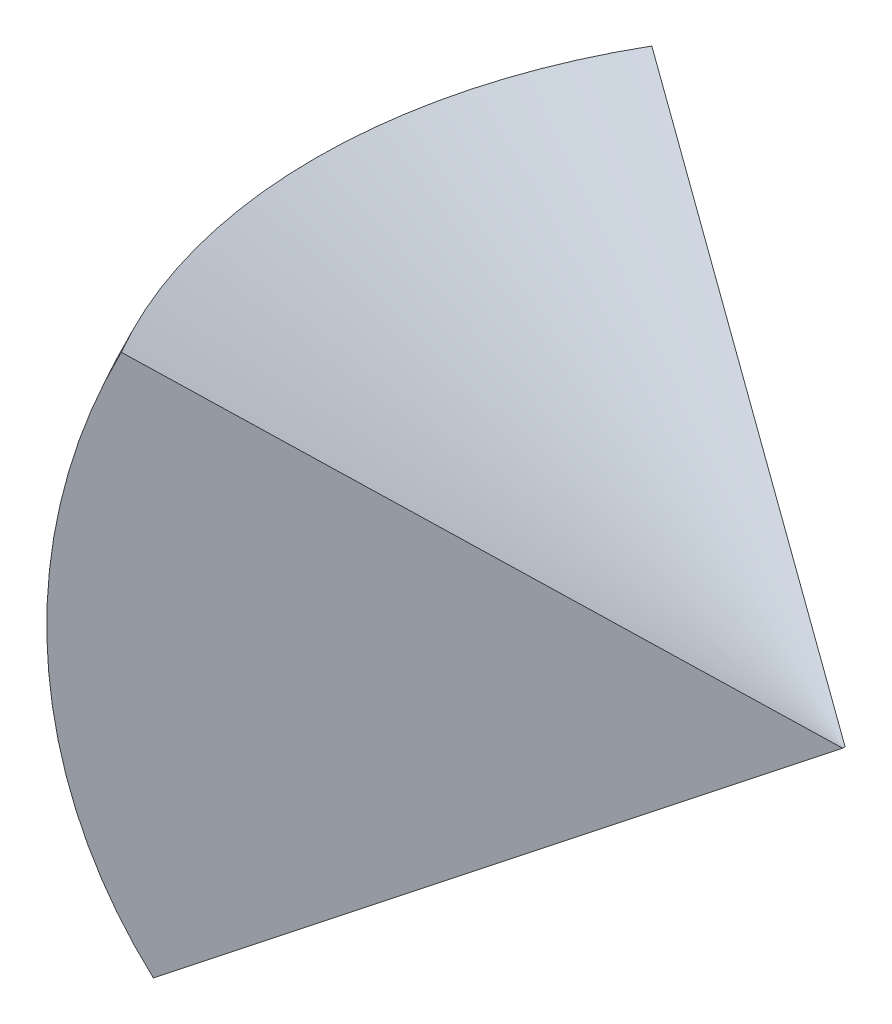
SolidWorks part; units mm, degrees
ref_plane "Plan de face" through (0, 0, 0) normal (0, 0, 1) x (1, 0, 0)
ref_plane "Plan de dessus" through (0, 0, 0) normal (0, 1, 0) x (1, 0, 0)
ref_plane "Plan de droite" through (0, 0, 0) normal (1, 0, 0) x (0, 0, -1)
sketch "Esquisse1" plane through (0, 0, 0) normal (0, 0, 1) x (1, 0, 0)
  line L0 (3.3856, 0) -> (-452.5492, 212.6059)
  line L1 (3.3856, 0) -> (-910.7226, 0) construction
  line L2 (3.3856, 0) -> (-432.2844, -251.5342)
  line L3 (5.4485, -756.0547) -> (5.4485, 353.0736) construction
  arc A0 (-452.5492, 212.6059) -> (-432.2844, -251.5342) centre (3.3856, 0) ccw
  dimension "D2" = 25
  dimension "D3" = 30
revolve "Révolution5" add sketch "Esquisse1" angle 60 mid plane about L3
ref_point "Point1"
ref_axis "Axe1" through (-445.5013, -18.908, 0.0298) along (0.9991, 0.0421, 0.0022)
ref_plane "Plan1" through (0.0054, -0.1289, -0.0031) normal (0.0421, -0.9988, -0.0243) x (0.9991, 0.0421, 0.0022)
